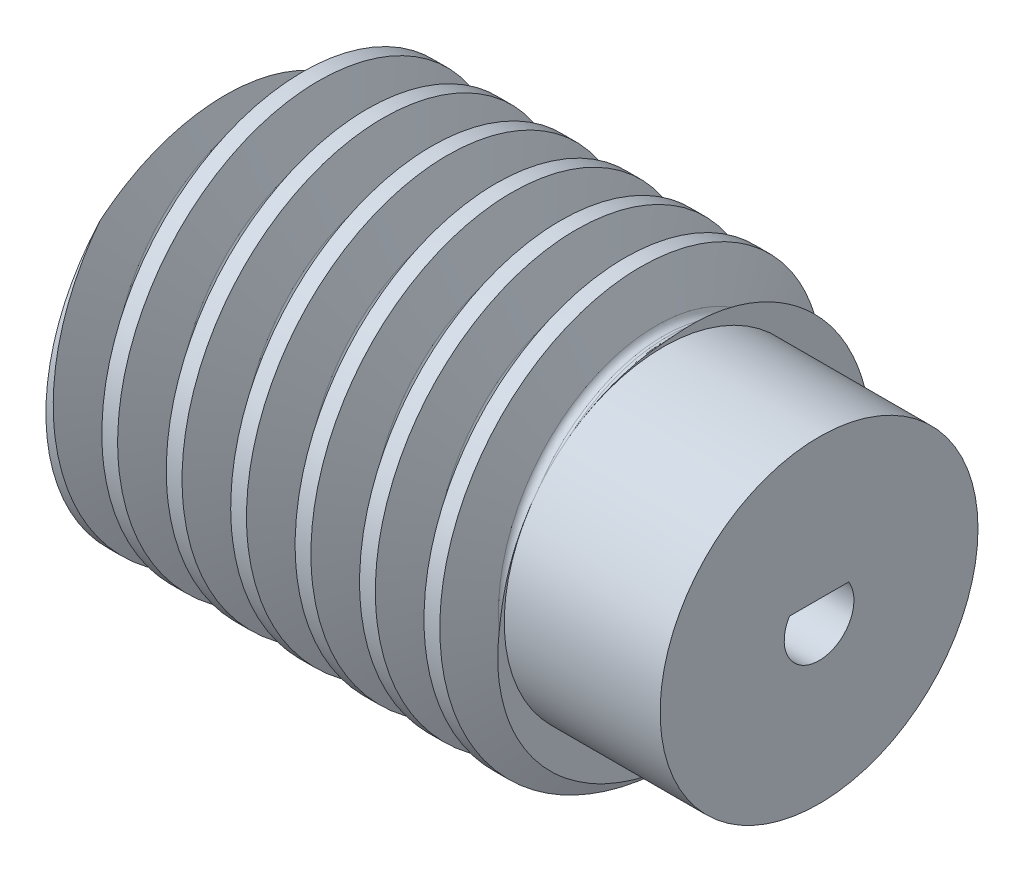
SolidWorks part; units mm, degrees
note: '?' marks a value the reader was unsure of.
ref_plane "前视基准面" through (0, 0, 0) normal (0, 0, 1) x (1, 0, 0)
ref_plane "上视基准面" through (0, 0, 0) normal (0, 1, 0) x (1, 0, 0)
ref_plane "右视基准面" through (0, 0, 0) normal (1, 0, 0) x (0, 0, -1)
ref_axis "基准轴1" through (-10.9638, 0, 0) along (1, 0, 0)?
sketch "草图1" plane through (0, 0, 0) normal (0, 0, 1) x (1, 0, 0)
  line L0 (-56.8494, 0) -> (118.6822, 0) construction
  line L1 (0, 48.1623) -> (0, -71.9241) construction
  line L2 (0, 10.1) -> (0, 0)
  line L3 (-10.9638, 0) -> (40.5935, 0) construction
  line L7 (0, 10.1) -> (20, 10.1)
  line L13 (0, 0) -> (20, 0)
  line L14 (20, 0) -> (20, 10.1)
  dimension "da1" = 10.1
  dimension "B1" = 20
revolve "旋转1" add sketch "草图1" angle 360 about L0
sketch "草图2" plane through (0, 0, 0) normal (1, 0, 0) x (0, 0, -1)
  circle A0 centre (0, 0) radius 9
  dimension "d1" = 18
sketch "草图3" plane through (0, 0, 0) normal (0, 0, 1) x (1, 0, 0)
  line L0 (0, 25.9401) -> (0, 0) construction
  line L1 (-3.5573, 10.1) -> (-1.1858, 10.1)
  line L2 (0, 10.1) -> (20, 10.1) construction
  line L3 (-1.1858, 10.1) -> (-1.9501, 8)
  line L4 (-2.3072, 7.75) -> (-2.4359, 7.75)
  line L5 (-2.3715, 10.1) -> (-2.3715, 7.75) construction
  line L6 (0, 0) -> (8.7963, 0) construction
  line L7 (-3.1569, 9) -> (-1.5861, 9) construction
  line L8 (-2.793, 8) -> (-3.5573, 10.1)
  line L9 (-3.5573, 10.1) -> (-3.5573, -9.9) construction
  line L10 (-2.3715, 10.1) -> (0, 10.1) construction
  arc A0 (-2.793, 8) -> (-2.4359, 7.75) centre (-2.4359, 8.13) ccw
  arc A1 (-2.3072, 7.75) -> (-1.9501, 8) centre (-2.3072, 8.13) ccw
  point P14 (-2.702, 7.75)
  point P19 (-2.0411, 7.75)
  dimension "ppn" = 0.38
  dimension "df1" = 15.5
  dimension "d1" = 18
  dimension "0.5px" = 1.5708
  dimension "aa1" = 20
  dimension "aa" = 20
sketch "草图4" plane through (0, 0, 0) normal (1, 0, 0) x (0, 0, -1)
  circle A0 centre (0, 0) radius 7.75
sketch "草图5" plane through (20, 0, 0) normal (1, 0, 0) x (0, 0, -1)
  circle A0 centre (0, 0) radius 7.75 construction
  circle A1 centre (0, 0) radius 7.75
curve "螺旋线/涡状线1" pitch 3.1416 height 30.4 turns 9.6766
sweep "切除-扫描1" cut profiles "草图3" path "螺旋线/涡状线1"
extrude "凸台-拉伸2" add sketch "草图5" along normal blind 7.6
sketch "草图6" plane through (27.6, 0, 0) normal (1, 0, 0) x (0, 0, -1)
  line L0 (-1.4422, 0.9) -> (1.4422, 0.9)
  line L1 (-14.3074, -1.7) -> (14.3074, -1.7) construction
  arc A0 (-1.4422, 0.9) -> (1.4422, 0.9) centre (0, 0) ccw
  point P8 (0, -1.7)
  dimension "D1" = 3.4
  dimension "D2" = 2.6
extrude "切除-拉伸1" cut sketch "草图6" against normal blind 20
